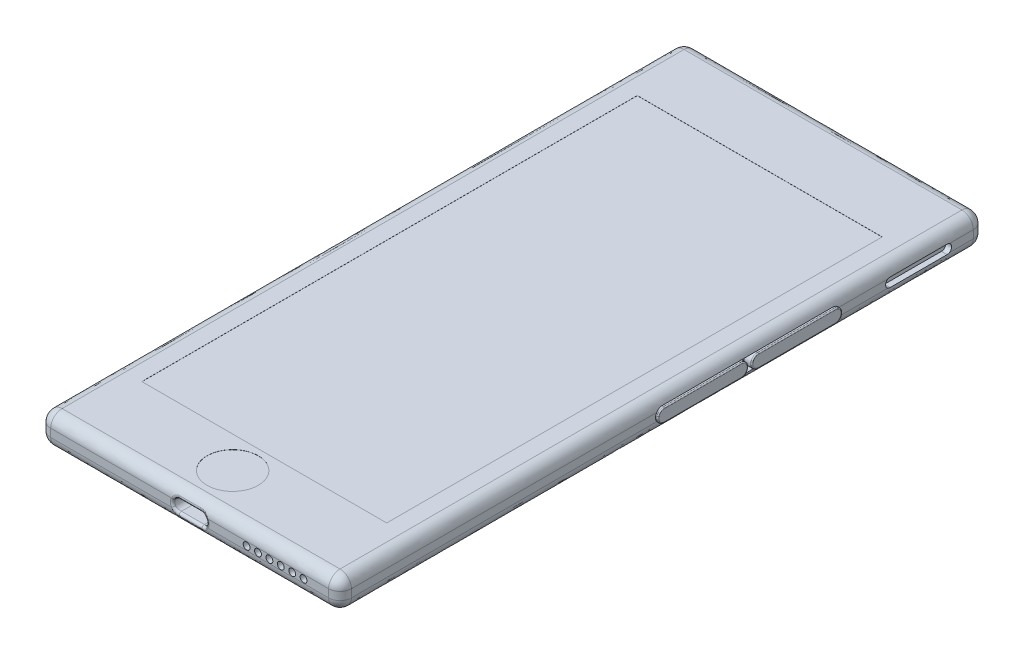
SolidWorks part; units mm, degrees
ref_plane "Front Plane" through (0, 0, 0) normal (0, 0, 1) x (1, 0, 0)
ref_plane "Top Plane" through (0, 0, 0) normal (0, 1, 0) x (1, 0, 0)
ref_plane "Right Plane" through (0, 0, 0) normal (1, 0, 0) x (0, 0, -1)
sketch "Sketch2" plane through (0, 0, 0) normal (0, 1, 0) x (1, 0, 0)
  line L1 (33.528, -71.882) -> (-33.528, -71.882)
  line L2 (33.528, -71.882) -> (33.528, 71.882)
  line L3 (33.528, 71.882) -> (-33.528, 71.882)
  line L4 (-33.528, -71.882) -> (-33.528, 71.882)
  line L5 (33.528, -71.882) -> (-33.528, 71.882) construction
  line L6 (33.528, 71.882) -> (-33.528, -71.882) construction
  point P1 (0, 0)
  dimension "D1" = 67.056
  dimension "D2" = 143.764
extrude "Boss-Extrude1" add sketch "Sketch2" along normal blind 6.858
fillet "Fillet1" radius 2.54 12 edges at (33.528, 0, 0) (0, 0, 71.882) (-33.528, 0, 0) (0, 0, -71.882) (-33.528, 3.429, -71.882) (33.528, 3.429, 71.882) (33.528, 3.429, -71.882) (-33.528, 3.429, 71.882) (0, 6.858, -71.882) (33.528, 6.858, 0) (0, 6.858, 71.882) (-33.528, 6.858, 0) first distance on face at (33.528, 3.429, 0) first distance on face at (0, 3.429, 71.882) first distance on face at (-33.528, 3.429, 0) first distance on face at (0, 3.429, -71.882)
sketch "Sketch3" plane through (0, 6.858, 0) normal (0, 1, 0) x (1, 0, 0)
  line L1 (27.305, -55.245) -> (-27.305, -55.245)
  line L2 (27.305, -55.245) -> (27.305, 55.245)
  line L3 (27.305, 55.245) -> (-27.305, 55.245)
  line L4 (-27.305, -55.245) -> (-27.305, 55.245)
  line L5 (27.305, -55.245) -> (-27.305, 55.245) construction
  line L6 (27.305, 55.245) -> (-27.305, -55.245) construction
  point P0 (0, 0)
  dimension "D1" = 54.61
  dimension "D2" = 110.49
extrude "Cut-Extrude1" cut sketch "Sketch3" against normal blind 0.0254
sketch "Sketch4" plane through (0, 6.858, 0) normal (0, 1, 0) x (1, 0, 0)
  line L0 (0, 0) -> (0, -55.245) construction
  line L1 (-27.305, -55.245) -> (27.305, -55.245) construction
  line L2 (0, -55.245) -> (0, -69.342) construction
  line L3 (-30.988, -69.342) -> (30.988, -69.342) construction
  circle A0 centre (0, -62.2935) radius 5.715
  point P7 (0, 0)
  point P11 (0, 0)
  point P12 (0, 0)
  point P13 (0, 0)
  point P14 (0, 0)
  point P15 (0, 0)
  point P16 (0, 0)
  point P17 (0, 0)
  point P18 (0, 0)
  point P19 (0, 0)
  point P20 (0, 0)
  point P21 (0, 0)
  point P22 (0, 0)
  point P23 (0, 0)
  point P24 (-21.8634, -63.4439)
  point P25 (0, 0)
  point P26 (0, -62.2935)
  dimension "D1" = 11.43
extrude "Cut-Extrude2" cut sketch "Sketch4" against normal blind 0.0254 contours A0
sketch "Sketch5" plane through (33.528, 0, 0) normal (1, 0, 0) x (0, 0, -1)
  line L0 (0, 4.318) -> (0, 2.54) construction
  line L1 (69.342, 4.318) -> (-69.342, 4.318) construction
  line L2 (-69.342, 2.54) -> (69.342, 2.54) construction
  line L3 (0, 2.54) -> (0, 0) construction
  line L4 (0, 0) -> (0, -6.2832) construction
  line L5 (0, 3.429) -> (38.1, 3.429) construction
  line L6 (38.1, 3.429) -> (50.8, 3.429) construction
  line L7 (50.8, 3.429) -> (58.42, 3.429) construction
  line L8 (58.42, 3.429) -> (63.5, 3.429) construction
  line L9 (0, 3.429) -> (38.1, 3.429) construction
  line L10 (0, 4.953) -> (38.1, 4.953)
  line L11 (0, 1.905) -> (38.1, 1.905)
  line L12 (50.8, 3.429) -> (63.5, 3.429) construction
  line L13 (50.8, 4.445) -> (63.5, 4.445)
  line L14 (50.8, 2.413) -> (63.5, 2.413)
  arc A0 (0, 4.953) -> (0, 1.905) centre (0, 3.429) ccw
  arc A1 (38.1, 1.905) -> (38.1, 4.953) centre (38.1, 3.429) ccw
  arc A2 (50.8, 4.445) -> (50.8, 2.413) centre (50.8, 3.429) ccw
  arc A3 (63.5, 2.413) -> (63.5, 4.445) centre (63.5, 3.429) ccw
  point P14 (19.05, 3.429)
  point P19 (57.15, 3.429)
  dimension "D1" = 38.1
  dimension "D2" = 12.7
  dimension "D3" = 7.62
  dimension "D4" = 5.08
  dimension "D5" = 3.048
  dimension "D6" = 2.032
extrude "Cut-Extrude3" cut sketch "Sketch5" against normal blind 1.27
sketch "Sketch6" plane through (32.258, 0, 0) normal (1, 0, 0) x (0, 0, -1)
  line L0 (0, 4.953) -> (0, 1.905) construction
  line L1 (0, 3.429) -> (17.145, 3.429) construction
  line L2 (17.145, 3.429) -> (20.955, 3.429) construction
  line L3 (38.1, 4.953) -> (38.1, 1.905) construction
  line L4 (38.1, 3.429) -> (20.955, 3.429) construction
  line L5 (0, 3.429) -> (17.145, 3.429) construction
  line L6 (0, 4.953) -> (17.145, 4.953)
  line L7 (0, 1.905) -> (17.145, 1.905)
  line L8 (38.1, 3.429) -> (20.955, 3.429) construction
  line L9 (38.1, 1.905) -> (20.955, 1.905)
  line L10 (38.1, 4.953) -> (20.955, 4.953)
  arc A0 (0, 4.953) -> (0, 1.905) centre (0, 3.429) ccw construction
  arc A1 (38.1, 1.905) -> (38.1, 4.953) centre (38.1, 3.429) ccw construction
  arc A2 (0, 4.953) -> (0, 1.905) centre (0, 3.429) ccw
  arc A3 (17.145, 1.905) -> (17.145, 4.953) centre (17.145, 3.429) ccw
  arc A4 (38.1, 1.905) -> (38.1, 4.953) centre (38.1, 3.429) ccw
  arc A5 (20.955, 4.953) -> (20.955, 1.905) centre (20.955, 3.429) ccw
  point P17 (8.5725, 3.429)
  point P22 (29.5275, 3.429)
  point P27 (0, 0)
  point P28 (0, 0)
  point P29 (0, 0)
  point P30 (0, 0)
  point P31 (0, 0)
  point P32 (0, 0)
  point P33 (0, 0)
  dimension "D1" = 3.81
extrude "Boss-Extrude4" add sketch "Sketch6" along normal blind 1.778
fillet "Fillet2" radius 0.254 8 edges at (34.036, 4.953, -29.5275) (34.036, 3.429, -39.624) (34.036, 1.905, -29.5275) (34.036, 3.429, -19.431) (34.036, 3.429, -18.669) (34.036, 4.953, -8.5725) (34.036, 3.429, 1.524) (34.036, 1.905, -8.5725)
sketch "Sketch8" plane through (0, 0, 71.882) normal (0, 0, 1) x (1, 0, 0)
  line L0 (0, 0) -> (0, 2.54) construction
  line L1 (-30.988, 2.54) -> (30.988, 2.54) construction
  line L2 (0, 2.54) -> (0, 4.318) construction
  line L3 (30.988, 4.318) -> (-30.988, 4.318) construction
  line L4 (0, 4.318) -> (0, 5.8597) construction
  line L5 (0, 3.429) -> (12.7, 3.429) construction
  circle A0 centre (12.7, 3.429) radius 0.762
  dimension "D2" = 1.524
  dimension "D1" = 12.7
extrude "Cut-Extrude5" cut sketch "Sketch8" against normal blind 1.778
pattern_linear "LPattern1" count 6 spacing 2.54 along (1, 0, 0) of "Cut-Extrude5"
sketch "Sketch9" plane through (0, 0, 71.882) normal (0, 0, 1) x (1, 0, 0)
  line L0 (0, 0) -> (0, 2.54) construction
  line L1 (-30.988, 2.54) -> (30.988, 2.54) construction
  line L2 (0, 2.54) -> (0, 4.318) construction
  line L3 (30.988, 4.318) -> (-30.988, 4.318) construction
  line L4 (0, 4.318) -> (0, 5.6539) construction
  line L5 (0, 3.429) -> (-2.54, 3.429) construction
  line L6 (0, 3.429) -> (2.54, 3.429) construction
  line L7 (-2.54, 3.429) -> (2.54, 3.429) construction
  line L8 (-2.54, 4.699) -> (2.54, 4.699)
  line L9 (-2.54, 2.159) -> (2.54, 2.159)
  arc A0 (-2.54, 4.699) -> (-2.54, 2.159) centre (-2.54, 3.429) ccw
  arc A1 (2.54, 2.159) -> (2.54, 4.699) centre (2.54, 3.429) ccw
  point P11 (0, 3.429)
  dimension "D1" = 2.54
  dimension "D2" = 2.54
extrude "Cut-Extrude6" cut sketch "Sketch9" against normal blind 3.81 contours L9 A0 L8 A1
fillet "Fillet3" radius 0.508 8 edges at (3.1029, 4.5674, 71.8697) (2.9591, 2.2301, 71.863) (0, 2.159, 71.8533) (-3.1029, 2.2906, 71.8697) (-2.9591, 4.6279, 71.863) (0, 4.699, 71.8533)
equation "\"0.27cmin\"=0.1"
